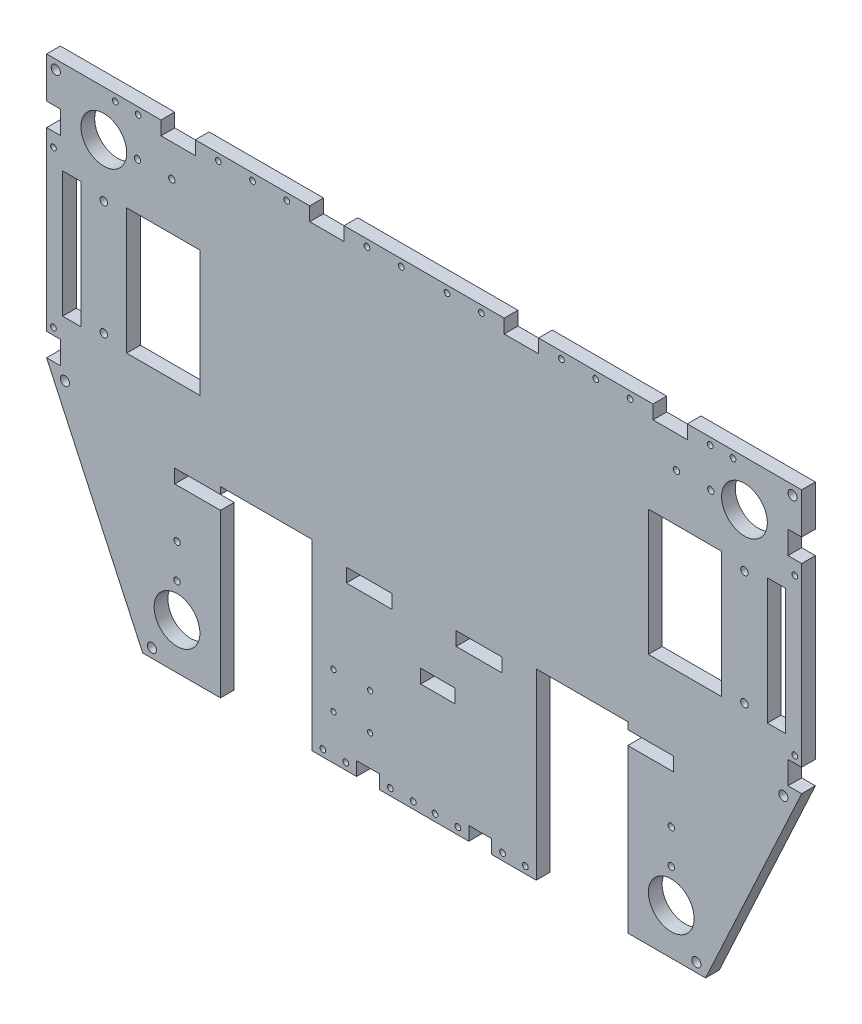
SolidWorks part; units mm, degrees
ref_plane "Plan de face" through (0, 0, 0) normal (0, 0, 1) x (1, 0, 0)
ref_plane "Plan de dessus" through (0, 0, 0) normal (0, 1, 0) x (1, 0, 0)
ref_plane "Plan de droite" through (0, 0, 0) normal (1, 0, 0) x (0, 0, -1)
sketch "Esquisse1" plane through (0, 0, 0) normal (0, 0, 1) x (1, 0, 0)
  line L0 (0, 124.9429) -> (0, -204.46) construction
  line L1 (-165, 96.73) -> (165, 96.73)
  line L2 (165, 96.73) -> (165, -18.27)
  line L3 (165, -18.27) -> (123, -109.0224)
  line L4 (123, -109.0224) -> (-123, -109.0224)
  line L5 (-211.9802, 0) -> (248.5953, 0) construction
  line L6 (-123, -109.0224) -> (-165, -18.27)
  line L7 (-165, -18.27) -> (-165, 96.73)
  line L9 (13.5, -54.0224) -> (-1.5, -54.0224)
  line L10 (13.5, -54.0224) -> (13.5, -60.0224)
  line L11 (13.5, -60.0224) -> (-1.5, -60.0224)
  line L12 (-1.5, -54.0224) -> (-1.5, -60.0224)
  circle A0 centre (-23.6, -89.5224) radius 1.15
  circle A1 centre (-23.6, -73.5224) radius 1.15
  circle A2 centre (-39.6, -89.5224) radius 1.15
  circle A3 centre (-39.6, -73.5224) radius 1.15
  dimension "D15" = 2.3
  dimension "D16" = 2.3
  dimension "D17" = 2.3
  dimension "D18" = 2.3
  dimension "D24" = 83.4
  dimension "D2" = 165
  dimension "D3" = 330
  dimension "D4" = 100
  dimension "D5" = 115
  dimension "D6" = 100
  dimension "D7" = 246
  dimension "D8" = 205.7524
  dimension "D9" = 96.73
  dimension "D10" = 115
  dimension "D11" = 6
  dimension "D12" = 15
  dimension "D13" = 49
  dimension "D14" = 109.5
  dimension "D19" = 19.5
  dimension "D20" = 16
  dimension "D21" = 16
  dimension "D22" = 16
  dimension "D23" = 16
extrude "Boss.-Extru.1" add sketch "Esquisse1" along normal blind 6
sketch "Esquisse2" plane through (0, 0, 6) normal (0, 0, 1) x (1, 0, 0)
  line L0 (-123, -109.0224) -> (123, -109.0224) construction
  line L1 (-158, 55.9776) -> (-150, 55.9776)
  line L2 (-158, 55.9776) -> (-158, 0.9776)
  line L3 (-158, 0.9776) -> (-150, 0.9776)
  line L4 (-150, 55.9776) -> (-150, 0.9776)
  line L5 (-130, 55.9776) -> (-98, 55.9776)
  line L6 (-130, 55.9776) -> (-130, 0.9776)
  line L7 (-130, 0.9776) -> (-98, 0.9776)
  line L8 (-98, 55.9776) -> (-98, 0.9776)
  line L9 (0, 145.0258) -> (0, -189.2208) construction
  line L10 (98, 55.9776) -> (98, 0.9776)
  line L11 (130, 0.9776) -> (98, 0.9776)
  line L12 (130, 55.9776) -> (130, 0.9776)
  line L13 (130, 55.9776) -> (98, 55.9776)
  line L14 (150, 55.9776) -> (150, 0.9776)
  line L15 (158, 0.9776) -> (150, 0.9776)
  line L16 (158, 55.9776) -> (158, 0.9776)
  line L17 (158, 55.9776) -> (150, 55.9776)
  line L19 (89, -109.0224) -> (89, -29.0224)
  line L20 (-49, -109.0224) -> (-89, -109.0224)
  line L21 (-49, -109.0224) -> (-49, -29.0224)
  line L22 (-49, -29.0224) -> (-89, -29.0224)
  line L23 (-89, -109.0224) -> (-89, -29.0224)
  line L24 (49, -29.0224) -> (89, -29.0224)
  line L25 (49, -109.0224) -> (49, -29.0224)
  line L26 (49, -109.0224) -> (89, -109.0224)
  line L27 (-165, 96.73) -> (-165, -18.27) construction
  line L28 (-123, -109.0224) -> (123, -109.0224) construction
  line L29 (165, -18.27) -> (165, 96.73) construction
  line L30 (165, 96.73) -> (-165, 96.73) construction
  circle A0 centre (140, 76.73) radius 10
  circle A1 centre (108, -89.0224) radius 10
  circle A2 centre (-140, 76.73) radius 10
  circle A3 centre (-108, -89.0224) radius 10
  circle A4 centre (157, -23.0224) radius 2
  circle A5 centre (119, -105.0224) radius 2
  circle A6 centre (161, 92.73) radius 2
  circle A7 centre (-161, 92.73) radius 2
  circle A8 centre (-157, -23.0224) radius 2
  circle A9 centre (-119, -105.0224) radius 2
  circle A10 centre (125.27, 76.73) radius 1.4
  circle A11 centre (110.27, 76.73) radius 1.4
  circle A12 centre (108, -74.2924) radius 1.4
  circle A13 centre (108, -59.2924) radius 1.4
  circle A14 centre (-110.27, 76.73) radius 1.4
  circle A15 centre (-125.27, 76.73) radius 1.4
  circle A16 centre (-108, -59.2924) radius 1.4
  circle A17 centre (-108, -74.2924) radius 1.4
  dimension "D16" = 20
  dimension "D17" = 20
  dimension "D18" = 15
  dimension "D19" = 20
  dimension "D20" = 25
  dimension "D21" = 20
  dimension "D24" = 8
  dimension "D15" = 4
  dimension "D25" = 4
  dimension "D28" = 4
  dimension "D29" = 4
  dimension "D30" = 2.8
  dimension "D31" = 2.8
  dimension "D34" = 2.8
  dimension "D35" = 2.8
  dimension "D2" = 8
  dimension "D3" = 20
  dimension "D4" = 32
  dimension "D5" = 98
  dimension "D6" = 55
  dimension "D7" = 55
  dimension "D8" = 110
  dimension "D9" = 110
  dimension "D10" = 40
  dimension "D11" = 80
  dimension "D12" = 76
  dimension "D13" = 98
  dimension "D14" = 7
  dimension "D22" = 4
  dimension "D23" = 4
  dimension "D26" = 24
  dimension "D27" = 4
  dimension "D32" = 14.73
  dimension "D33" = 15
  dimension "D36" = 14.73
  dimension "D37" = 15
extrude "Enlèv. mat.-Extru.1" cut sketch "Esquisse2" against normal blind 6
sketch "Esquisse3" plane through (0, 0, 0) normal (0, 0, -1) x (-1, 0, 0)
  line L0 (165, 96.73) -> (165, -18.27) construction
  line L1 (165, -18.27) -> (159, -18.27)
  line L2 (165, -18.27) -> (165, -8.27)
  line L3 (165, -8.27) -> (159, -8.27)
  line L4 (159, -18.27) -> (159, -8.27)
  line L5 (49, -109.0224) -> (-49, -109.0224) construction
  line L6 (165, 68.8526) -> (159, 68.8526)
  line L7 (165, 68.8526) -> (165, 78.8526)
  line L8 (165, 78.8526) -> (159, 78.8526)
  line L9 (159, 68.8526) -> (159, 78.8526)
  line L10 (29.5, -109.0224) -> (19.5, -109.0224)
  line L11 (29.5, -109.0224) -> (29.5, -103.0224)
  line L12 (29.5, -103.0224) -> (19.5, -103.0224)
  line L13 (19.5, -109.0224) -> (19.5, -103.0224)
  line L14 (49, -109.0224) -> (49, -29.0224) construction
  line L15 (0, -209.4812) -> (0, 177.1799) construction
  line L17 (150, 55.9776) -> (158, 55.9776) construction
  line L18 (-19.5, -109.0224) -> (-19.5, -103.0224)
  line L19 (-29.5, -103.0224) -> (-19.5, -103.0224)
  line L20 (-29.5, -109.0224) -> (-29.5, -103.0224)
  line L21 (-29.5, -109.0224) -> (-19.5, -109.0224)
  line L22 (-159, 68.8526) -> (-159, 78.8526)
  line L23 (-165, 78.8526) -> (-159, 78.8526)
  line L24 (-165, 68.8526) -> (-165, 78.8526)
  line L25 (-165, 68.8526) -> (-159, 68.8526)
  line L26 (-159, -18.27) -> (-159, -8.27)
  line L27 (-165, -8.27) -> (-159, -8.27)
  line L28 (-165, -18.27) -> (-165, -8.27)
  line L29 (-165, -18.27) -> (-159, -18.27)
  line L30 (-165, 96.73) -> (165, 96.73) construction
  line L31 (115, 96.73) -> (100, 96.73)
  line L32 (115, 96.73) -> (115, 90.73)
  line L33 (115, 90.73) -> (100, 90.73)
  line L34 (100, 96.73) -> (100, 90.73)
  line L35 (-35, 96.73) -> (-35, 90.73)
  line L36 (50, 96.73) -> (35, 96.73)
  line L37 (50, 96.73) -> (50, 90.73)
  line L38 (50, 90.73) -> (35, 90.73)
  line L39 (35, 96.73) -> (35, 90.73)
  line L40 (-50, 90.73) -> (-35, 90.73)
  line L41 (-50, 96.73) -> (-50, 90.73)
  line L42 (-50, 96.73) -> (-35, 96.73)
  line L43 (-100, 96.73) -> (-100, 90.73)
  line L44 (-115, 90.73) -> (-100, 90.73)
  line L45 (-115, 96.73) -> (-115, 90.73)
  line L46 (-115, 96.73) -> (-100, 96.73)
  dimension "D1" = 10
  dimension "D2" = 6
  dimension "D3" = 6
  dimension "D4" = 10
  dimension "D5" = 10
  dimension "D6" = 6
  dimension "D7" = 19.5
  dimension "D9" = 12.875
  dimension "D10" = 15
  dimension "D11" = 15
  dimension "D12" = 50
  dimension "D13" = 50
  dimension "D14" = 6
extrude "Enlèv. mat.-Extru.2" cut sketch "Esquisse3" against normal blind 6
sketch "Esquisse4" plane through (0, 0, 0) normal (0, 0, -1) x (-1, 0, 0)
  line L0 (159, 68.8526) -> (165, 68.8526) construction
  line L2 (54.0695, -106.0224) -> (4.75, -106.0224) construction
  line L3 (49, -109.0224) -> (29.5, -109.0224) construction
  line L4 (49, -109.0224) -> (49, -29.0224) construction
  line L5 (19.5, -103.0224) -> (19.5, -109.0224) construction
  line L8 (165, 68.8526) -> (165, -8.27) construction
  line L11 (143.8632, 93.73) -> (10, 93.73) construction
  line L12 (50, 96.73) -> (100, 96.73) construction
  line L13 (115, 90.73) -> (115, 96.73) construction
  line L14 (100, 96.73) -> (100, 90.73) construction
  line L15 (50, 90.73) -> (50, 96.73) construction
  line L16 (35, 96.73) -> (35, 90.73) construction
  line L17 (0, 142.2997) -> (0, -202.2086) construction
  line L18 (-143.8632, 93.73) -> (-10, 93.73) construction
  line L19 (-54.0695, -106.0224) -> (-4.75, -106.0224) construction
  line L21 (165, -8.27) -> (159, -8.27) construction
  circle A0 centre (162, -5.27) radius 1.25
  circle A2 centre (162, 62.8526) radius 1.25
  circle A6 centre (44.25, -106.0224) radius 1.25
  circle A7 centre (14.75, -106.0224) radius 1.25
  circle A8 centre (4.75, -106.0224) radius 1.25
  circle A9 centre (34.2497, -106.0224) radius 1.25
  circle A10 centre (135, 93.73) radius 1.25
  circle A11 centre (125, 93.73) radius 1.25
  circle A12 centre (90, 93.73) radius 1.25
  circle A13 centre (75, 93.73) radius 1.25
  circle A14 centre (60, 93.73) radius 1.25
  circle A15 centre (25, 93.73) radius 1.25
  circle A16 centre (10, 93.73) radius 1.25
  circle A17 centre (-10, 93.73) radius 1.25
  circle A18 centre (-25, 93.73) radius 1.25
  circle A19 centre (-60, 93.73) radius 1.25
  circle A20 centre (-75, 93.73) radius 1.25
  circle A21 centre (-90, 93.73) radius 1.25
  circle A22 centre (-125, 93.73) radius 1.25
  circle A23 centre (-135, 93.73) radius 1.25
  circle A24 centre (-34.2497, -106.0224) radius 1.25
  circle A25 centre (-4.75, -106.0224) radius 1.25
  circle A26 centre (-14.75, -106.0224) radius 1.25
  circle A27 centre (-44.25, -106.0224) radius 1.25
  circle A31 centre (-162, 62.8526) radius 1.25
  circle A33 centre (-162, -5.27) radius 1.25
  dimension "D3" = 2.5
  dimension "D10" = 2.5
  dimension "D11" = 2.5
  dimension "D12" = 2.5
  dimension "D13" = 2.5
  dimension "D14" = 10.0003
  dimension "D18" = 3
  dimension "D19" = 2.5
  dimension "D29" = 2.5
  dimension "D30" = 2.5
  dimension "D31" = 2.5
  dimension "D32" = 2.5
  dimension "D33" = 2.5
  dimension "D34" = 2.5
  dimension "D35" = 2.5
  dimension "D40" = 10
  dimension "D5" = 3
  dimension "D6" = 6
  dimension "D9" = 3
  dimension "D15" = 4.75
  dimension "D16" = 10
  dimension "D17" = 4.75
  dimension "D26" = 3
  dimension "D28" = 3
  dimension "D36" = 10
  dimension "D37" = 10
  dimension "D38" = 10
  dimension "D39" = 15
  dimension "D41" = 15
  dimension "D42" = 10
extrude "Enlèv. mat.-Extru.3" cut sketch "Esquisse4" against normal blind 6
sketch "Esquisse5" plane through (0, 0, 0) normal (0, 0, -1) x (-1, 0, 0)
  line L0 (89, -29.0224) -> (89, -109.0224) construction
  line L1 (89, -38.0224) -> (109, -38.0224)
  line L2 (89, -38.0224) -> (89, -32.0224)
  line L3 (89, -32.0224) -> (109, -32.0224)
  line L4 (109, -38.0224) -> (109, -32.0224)
  line L5 (0, -159.6455) -> (0, 113.5094) construction
  line L6 (34, -38.0224) -> (14, -38.0224)
  line L7 (34, -38.0224) -> (34, -32.0224)
  line L8 (34, -32.0224) -> (14, -32.0224)
  line L9 (14, -38.0224) -> (14, -32.0224)
  line L10 (49, -109.0224) -> (49, -29.0224) construction
  line L11 (-14, -38.0224) -> (-14, -32.0224)
  line L12 (-34, -32.0224) -> (-14, -32.0224)
  line L13 (-34, -38.0224) -> (-34, -32.0224)
  line L14 (-34, -38.0224) -> (-14, -38.0224)
  line L15 (-109, -38.0224) -> (-109, -32.0224)
  line L16 (-89, -32.0224) -> (-109, -32.0224)
  line L17 (-89, -38.0224) -> (-89, -32.0224)
  line L18 (-89, -38.0224) -> (-109, -38.0224)
  line L22 (49, -29.0224) -> (89, -29.0224) construction
  dimension "D1" = 20
  dimension "D2" = 20
  dimension "D3" = 15
  dimension "D4" = 6
  dimension "D5" = 6
  dimension "D6" = 3
  dimension "D7" = 3
extrude "Enlèv. mat.-Extru.4" cut sketch "Esquisse5" against normal blind 6
sketch "Esquisse6" plane through (0, 0, 0) normal (0, 0, -1) x (-1, 0, 0)
  line L0 (-159, -8.27) -> (-165, -8.27) construction
  line L1 (-165, -8.27) -> (-165, 68.8526) construction
  line L2 (0, 127.7926) -> (0, -140.3318) construction
  circle A0 centre (-140, 3.48) radius 1.65
  circle A1 centre (-140, 53.48) radius 1.65
  circle A2 centre (140, 53.48) radius 1.65
  circle A3 centre (140, 3.48) radius 1.65
  dimension "D1" = 3.3
  dimension "D2" = 3.3
  dimension "D3" = 11.75
  dimension "D4" = 25
  dimension "D5" = 25
  dimension "D6" = 50
extrude "Enlèv. mat.-Extru.5" cut sketch "Esquisse6" against normal blind 6
